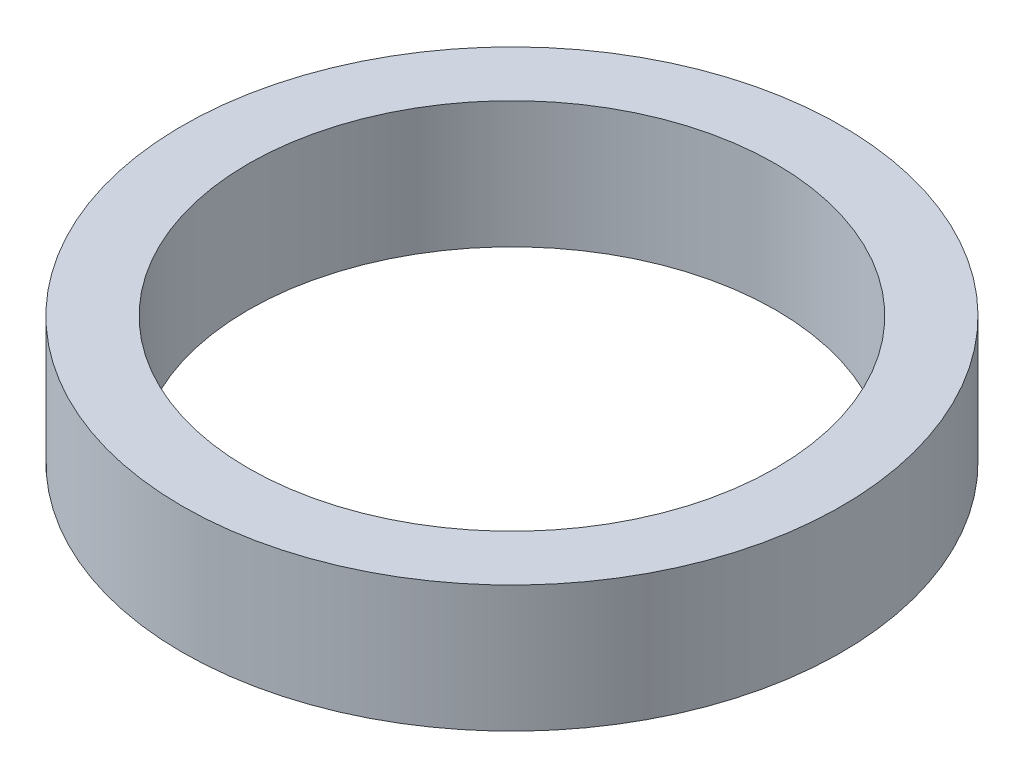
SolidWorks part; units mm, degrees
ref_plane "Front Plane" through (0, 0, 0) normal (0, 0, 1) x (1, 0, 0)
ref_plane "Top Plane" through (0, 0, 0) normal (0, 1, 0) x (1, 0, 0)
ref_plane "Right Plane" through (0, 0, 0) normal (1, 0, 0) x (0, 0, -1)
sketch "Sketch1" plane through (0, 0, 0) normal (0, 1, 0) x (1, 0, 0)
  circle A0 centre (0, 0) radius 62.5
  dimension "FLANGE_OD" = 125
extrude "Boss-Extrude1" add sketch "Sketch1" along normal blind 24
sketch "Sketch2" plane through (0, 0, 0) normal (0, 1, 0) x (1, 0, 0)
  circle A0 centre (0, 0) radius 50
  dimension "BORE_D" = 100
extrude "Cut-Extrude1" cut sketch "Sketch2" along normal through all
sketch "Sketch3" plane through (0, 24, 0) normal (0, 1, 0) x (1, 0, 0)
  circle A0 centre (0, 0) radius 28.657 construction
  circle A1 centre (-28.657, 0) radius 2.2428
  dimension "BOLT_D" = 4.4855
  dimension "BOLT_PCD" = 57.314
extrude "Cut-Extrude2" cut sketch "Sketch3" against normal blind 20.1622 rebuild error yes
pattern_circular "CirPattern1" count 6 over 360 rebuild error yes
